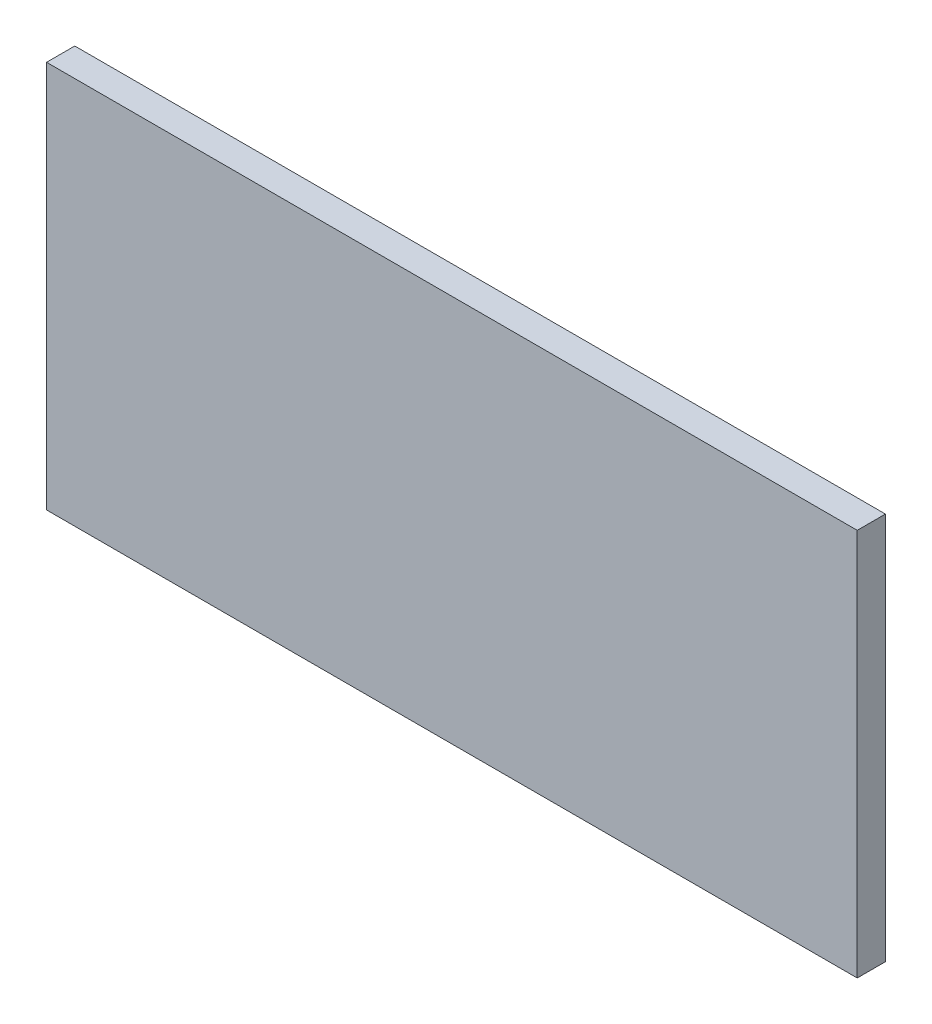
SolidWorks part; units mm, degrees
ref_plane "前视基准面" through (0, 0, 0) normal (0, 0, 1) x (1, 0, 0)
ref_plane "上视基准面" through (0, 0, 0) normal (0, 1, 0) x (1, 0, 0)
ref_plane "右视基准面" through (0, 0, 0) normal (1, 0, 0) x (0, 0, -1)
other "Configuration Table"
sketch "草图1" plane through (0, 0, 0) normal (0, 0, 1) x (1, 0, 0)
  line L1 (-115, 55) -> (115, 55)
  line L2 (-115, 55) -> (-115, -55)
  line L3 (-115, -55) -> (115, -55)
  line L4 (115, 55) -> (115, -55)
  line L5 (-115, 55) -> (115, -55) construction
  line L6 (-115, -55) -> (115, 55) construction
  point P0 (0, 0)
  dimension "D1" = 230
  dimension "D2" = 110
extrude "凸台-拉伸2" add sketch "草图1" along normal blind 8
sketch "草图2" plane through (0, 0, 8) normal (0, 0, 1) x (1, 0, 0)
  line L0 (115, 55) -> (-115, 55) construction
  line L1 (-115, 55) -> (-115, -55) construction
  line L2 (-115, -55) -> (115, -55) construction
  line L3 (115, -55) -> (115, 55) construction
  circle A0 centre (-105, 45) radius 3
  circle A1 centre (-105, -45) radius 3
  circle A2 centre (105, -45) radius 3
  circle A3 centre (105, 45) radius 3
  dimension "D1" = 6
  dimension "D4" = 6
  dimension "D7" = 6
  dimension "D10" = 6
  dimension "D2" = 10
  dimension "D3" = 10
  dimension "D5" = 10
  dimension "D6" = 10
  dimension "D8" = 10
  dimension "D9" = 10
  dimension "D11" = 10
  dimension "D12" = 10
